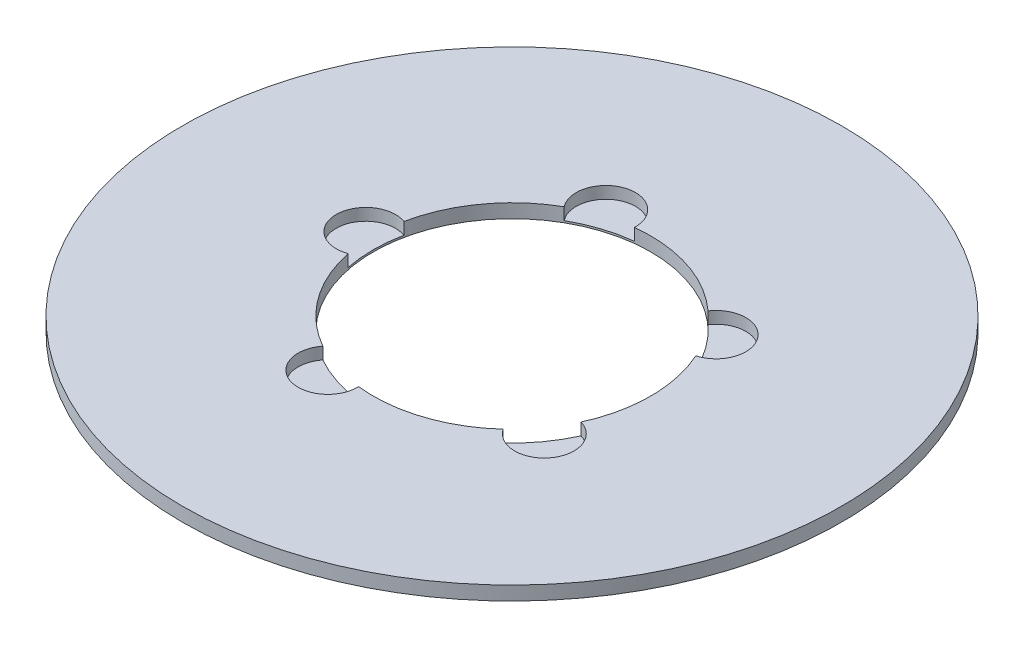
SolidWorks part; units mm, degrees
ref_plane "Front Plane" through (0, 0, 0) normal (0, 0, 1) x (1, 0, 0)
ref_plane "Top Plane" through (0, 0, 0) normal (0, 1, 0) x (1, 0, 0)
ref_plane "Right Plane" through (0, 0, 0) normal (1, 0, 0) x (0, 0, -1)
sketch "Sketch1" plane through (0, 0, 0) normal (0, 1, 0) x (1, 0, 0)
  circle A0 centre (0, 0) radius 95
  dimension "FLANGE_OD" = 190
extrude "Boss-Extrude1" add sketch "Sketch1" along normal blind 4
sketch "Sketch2" plane through (0, 0, 0) normal (0, 1, 0) x (1, 0, 0)
  circle A0 centre (0, 0) radius 40
  dimension "BORE_D" = 80
extrude "Cut-Extrude1" cut sketch "Sketch2" along normal through all
sketch "Sketch3" plane through (0, 4, 0) normal (0, 1, 0) x (1, 0, 0)
  circle A0 centre (0, 0) radius 42.1348 construction
  circle A1 centre (-42.1348, 0) radius 8.5497
  dimension "BOLT_D" = 17.0993
  dimension "BOLT_PCD" = 84.2696
extrude "Cut-Extrude2" cut sketch "Sketch3" against normal blind 3.4539
pattern_circular "CirPattern1" count 5 over 360 about axis through (0, 0, 0) along (0, 1, 0) of "Cut-Extrude2"
